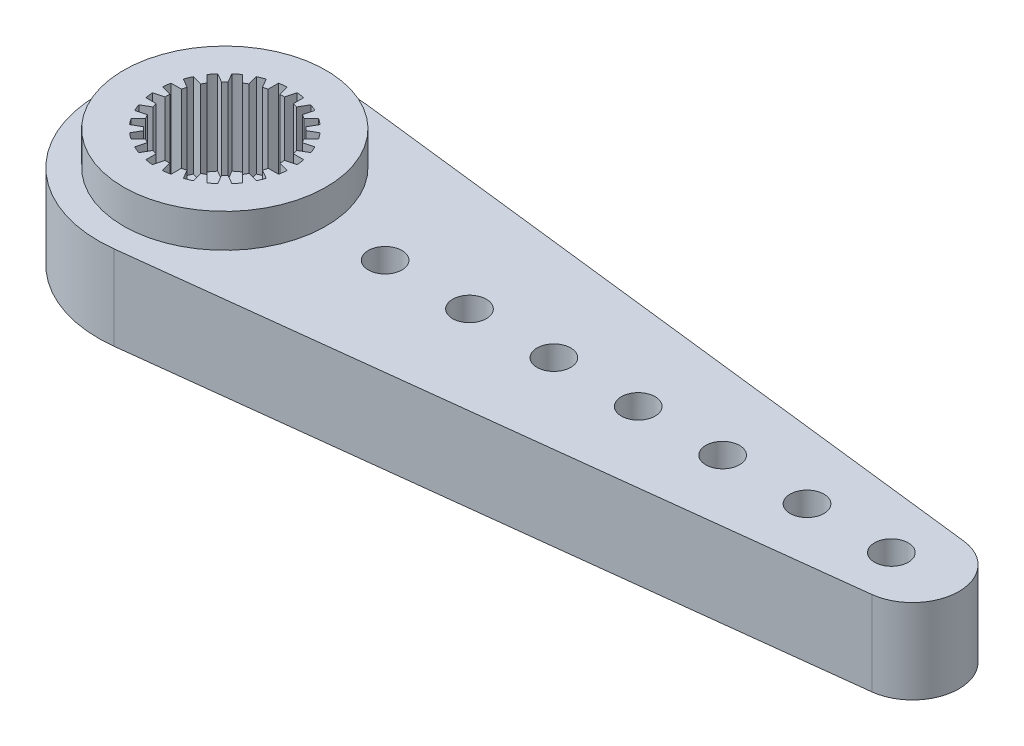
SolidWorks part; units mm, degrees
ref_plane "Plan de face" through (0, 0, 0) normal (0, 0, 1) x (1, 0, 0)
ref_plane "Plan de dessus" through (0, 0, 0) normal (0, 1, 0) x (1, 0, 0)
ref_plane "Plan de droite" through (0, 0, 0) normal (1, 0, 0) x (0, 0, -1)
sketch "Esquisse1" plane through (0, 0, 0) normal (0, 1, 0) x (1, 0, 0)
  line L0 (0.8742, -7.4489) -> (41.0706, -2.7313)
  line L1 (41.0706, 2.7313) -> (0.8742, 7.4489)
  line L2 (-7.5, 27.3999) -> (-7.5, -15.4168) construction
  line L3 (-7.5, -15.4168) -> (43.5, -15.4168) construction
  line L4 (43.5, -15.4168) -> (43.5, 24.8813) construction
  arc A0 (0.8742, 7.4489) -> (0.8742, -7.4489) centre (0, 0) ccw
  arc A1 (41.0706, -2.7313) -> (41.0706, 2.7313) centre (40.75, 0) ccw
  circle A2 centre (0, 0) radius 1.6
  dimension "D1" = 2.75
  dimension "D2" = 7.5
  dimension "D4" = 3.2
  dimension "D3" = 51
extrude "Boss.-Extru.1" add sketch "Esquisse1" along normal blind 8
sketch "Esquisse2" plane through (0, 8, 0) normal (0, 1, 0) x (1, 0, 0)
  line L0 (0, 0) -> (46.1588, 0) construction
  line L1 (-7.5, 15.192) -> (-7.5, -12.3349) construction
  circle A0 centre (9.5, 0) radius 1
  arc A1 (0.8742, 7.4489) -> (0.8742, -7.4489) centre (0, 0) ccw construction
  dimension "D1" = 2
  dimension "D2" = 17
extrude "Enlèv. mat.-Extru.1" cut sketch "Esquisse2" against normal blind 8
pattern_linear "Répétition linéaire1" count 7 spacing 5 along (1, 0, 0) of "Enlèv. mat.-Extru.1"
sketch "Esquisse3" plane through (0, 8, 0) normal (0, 1, 0) x (1, 0, 0)
  line L1 (-12.783, 10.2172) -> (50.2427, 10.2172)
  line L2 (-12.783, 10.2172) -> (-12.783, -12.2303)
  line L3 (-12.783, -12.2303) -> (50.2427, -12.2303)
  line L4 (50.2427, 10.2172) -> (50.2427, -12.2303)
  circle A0 centre (0, 0) radius 6
  dimension "D1" = 12
extrude "Enlèv. mat.-Extru.2" cut sketch "Esquisse3" against normal blind 2
sketch "Esquisse4" plane through (0, 0, 0) normal (0, -1, 0) x (1, 0, 0)
  line L1 (-13.4769, 12.3588) -> (51.6733, 12.3588)
  line L2 (-13.4769, 12.3588) -> (-13.4769, -11.2271)
  line L3 (-13.4769, -11.2271) -> (51.6733, -11.2271)
  line L4 (51.6733, 12.3588) -> (51.6733, -11.2271)
  circle A0 centre (0, 0) radius 4.65
  dimension "D1" = 9.3
extrude "Enlèv. mat.-Extru.3" cut sketch "Esquisse4" against normal blind 1
sketch "Esquisse5" plane through (0, 0, 0) normal (0, -1, 0) x (1, 0, 0)
  circle A0 centre (0, 0) radius 2.75
  dimension "D1" = 5.5
extrude "Enlèv. mat.-Extru.4" cut sketch "Esquisse5" against normal blind 1
chamfer "Chanfrein1" distance 1 angle 45 1 edges at (0, 1, -4.65)
sketch "Esquisse6" plane through (0, 8, 0) normal (0, 1, 0) x (1, 0, 0)
  circle A0 centre (0, 0) radius 4
  dimension "D1" = 8
extrude "Enlèv. mat.-Extru.5" cut sketch "Esquisse6" against normal blind 5
sketch "Esquisse7" plane through (0, 8, 0) normal (0, 1, 0) x (1, 0, 0)
  line L0 (0, 0) -> (0, -6.8034) construction
  line L1 (0, -6.8034) -> (2.7804, -4) construction
  line L2 (2.7804, -4) -> (-2.8896, -4) construction
  line L3 (0.3, -4) -> (0.1392, -3.4)
  line L4 (0.1392, -3.4) -> (-0.1392, -3.4)
  line L5 (-0.1392, -3.4) -> (-0.3, -4)
  line L6 (-0.3, -4) -> (0.3, -4)
  circle A0 centre (0, 0) radius 4 construction
  dimension "D1" = 0.6
  dimension "D2" = 0.6
  dimension "D3" = 15
extrude "Boss.-Extru.2" add sketch "Esquisse7" against normal up to surface (5 mm away) up to face at (0, 3, 1.6)
pattern_circular "Répétition circulaire1" count 24 over 360 about axis through (0, 8, 0) along (0, -1, 0) of "Boss.-Extru.2"
scale "Escala2" scale about centroid uniform scaling yes scale factor 0.7
scale "Escala5" scale about centroid uniform scaling yes scale factor 0.8
scale "Escala6" scale about centroid uniform scaling yes scale factor 0.9
scale "Escala7" scale about centroid uniform scaling yes scale factor 0.9
scale "Escala8" scale about centroid uniform scaling yes scale factor 1.05
scale "Escala9" scale about centroid uniform scaling yes scale factor 1.2
scale "Escala11" bodies to scale 118 scale about centroid uniform scaling yes scale factor 0.8
